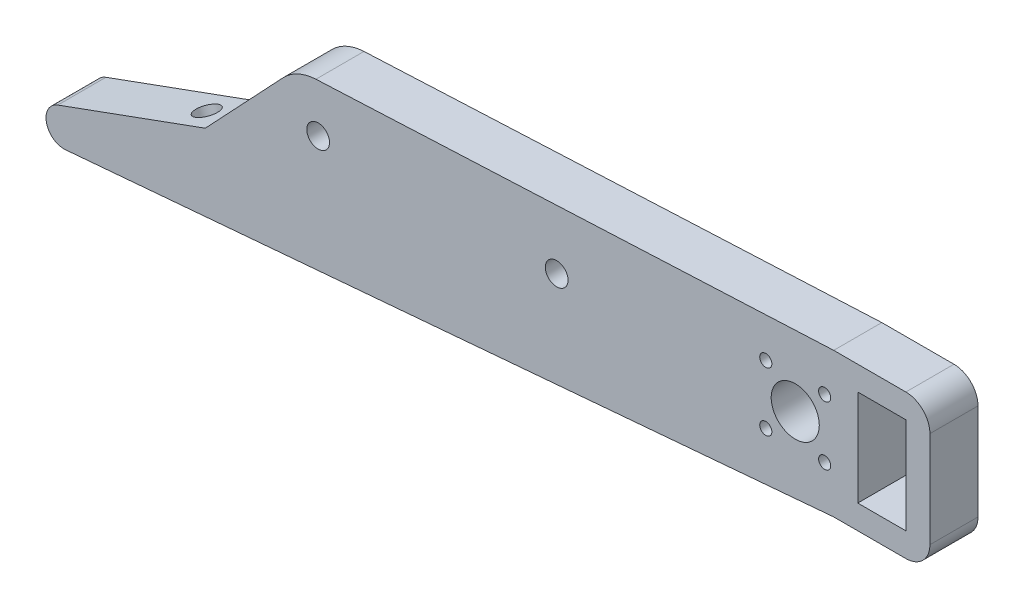
SolidWorks part; units mm, degrees
ref_plane "Front Plane" through (0, 0, 0) normal (0, 0, 1) x (1, 0, 0)
ref_plane "Top Plane" through (0, 0, 0) normal (0, 1, 0) x (1, 0, 0)
ref_plane "Right Plane" through (0, 0, 0) normal (1, 0, 0) x (0, 0, -1)
sketch "Sketch1" plane through (0, 0, 0) normal (0, 0, 1) x (1, 0, 0)
  line L0 (27.6069, 3.8891) -> (35.3851, -3.8891) construction
  line L1 (0, -55) -> (0, 55) construction
  line L2 (27.6069, -3.8891) -> (35.3851, 3.8891) construction
  line L3 (-1001.9207, 0) -> (48998.0793, 0) construction
  line L4 (-969.6313, -19.05) -> (49030.3687, -19.05) construction
  line L5 (36.576, 9.525) -> (49.276, 9.525)
  line L6 (39.751, 6.35) -> (46.101, 6.35)
  line L7 (39.751, 6.35) -> (39.751, -6.35)
  line L8 (39.751, -6.35) -> (46.101, -6.35)
  line L9 (46.101, 6.35) -> (46.101, -6.35)
  line L10 (39.751, 6.35) -> (46.101, -6.35) construction
  line L11 (39.751, -6.35) -> (46.101, 6.35) construction
  line L13 (36.576, -9.525) -> (49.276, -9.525)
  line L14 (36.576, 0) -> (36.576, -9.525) construction
  line L15 (49.276, 9.525) -> (49.276, -9.525)
  line L21 (36.576, 9.525) -> (36.576, 0) construction
  line L22 (36.576, 9.525) -> (36.576, -9.525) construction
  line L23 (-46.398, -6.562) -> (-80.7085, -19.05) construction
  line L24 (49.276, 9.525) -> (49.276, -9.525) construction
  line L25 (36.576, 9.525) -> (-31.7912, 6.3431)
  line L26 (-36.1188, 4.3534) -> (-46.398, -6.562)
  line L27 (-46.398, -6.562) -> (-65.8615, -13.6461)
  line L28 (-64.8428, -18.2563) -> (36.576, -9.525)
  circle A0 centre (31.496, 0) radius 3.175
  circle A1 centre (27.6069, 3.8891) radius 0.8
  circle A2 centre (35.3851, -3.8891) radius 0.8
  circle A4 centre (-31.496, 0) radius 1.5
  circle A5 centre (35.3851, 3.8891) radius 0.8
  circle A6 centre (27.6069, -3.8891) radius 0.8
  circle A7 centre (31.496, 0) radius 19.05 construction
  circle A8 centre (-31.496, 0) radius 19.05 construction
  arc A16 (-31.7912, 6.3431) -> (-36.1188, 4.3534) centre (-31.496, 0) ccw
  circle A17 centre (-29.9085, 22.225) radius 38.1 construction
  arc A18 (-65.8615, -13.6461) -> (-64.8428, -18.2563) centre (-65.0471, -15.8838) ccw
  arc A19 (-37.846, 0) -> (-25.146, 0) centre (-31.496, 0) ccw construction
  arc A21 (-25.146, 0) -> (-31.7912, 6.3431) centre (-31.496, 0) ccw construction
  arc A22 (-36.1188, 4.3534) -> (-37.846, 0) centre (-31.496, 0) ccw construction
  circle A23 centre (0, 0) radius 1.5
  point P6 (31.496, 0)
  point P17 (31.496, 0)
  point P33 (42.926, 0)
  point P51 (-29.9085, -15.875)
  point P52 (-68.0085, 22.225)
  dimension "D1" = 6.35
  dimension "D3" = 62.992
  dimension "D4" = 1.6
  dimension "D7" = 38.1
  dimension "D10" = 12.7
  dimension "D11" = 36.5125
  dimension "D16" = 1.5875
  dimension "D18" = 76.2
  dimension "D6" = 3
  dimension "D9" = 12.7
  dimension "D19" = 4.7625
  dimension "D2" = 11
  dimension "D5" = 45
  dimension "D8" = 20
  dimension "D12" = 6.35
  dimension "D13" = 12.7
  dimension "D15" = 11.43
  dimension "D17" = 3.175
  dimension "D20" = 1.5875
  dimension "D14" = 3.175
extrude "Boss-Extrude1" add sketch "Sketch1" along normal mid plane 6.35 contours L27 A18 L28 L13 L15 L5 L25 A16 L26 A4 A2 A1 A0 L6 L9 L8 L7 A5 A6 region at (-5.0143, -3.6936, 0)
fillet "Fillet1" radius 3.175 2 edges at (49.276, -9.525, 0) (49.276, 9.525, 0)
sketch "Sketch2" plane through (-3.3185, 9.1176, 0) normal (-0.342, 0.9397, 0) x (0.9397, 0.342, 0)
  line L1 (-49.0192, 0) -> (-45.8442, 0) construction
  line L2 (-45.8442, -3.175) -> (-45.8442, 3.175) construction
  circle A0 centre (-49.0192, 0) radius 1.5
  dimension "D2" = 3.175
extrude "Cut-Extrude1" cut sketch "Sketch2" against normal blind 6
